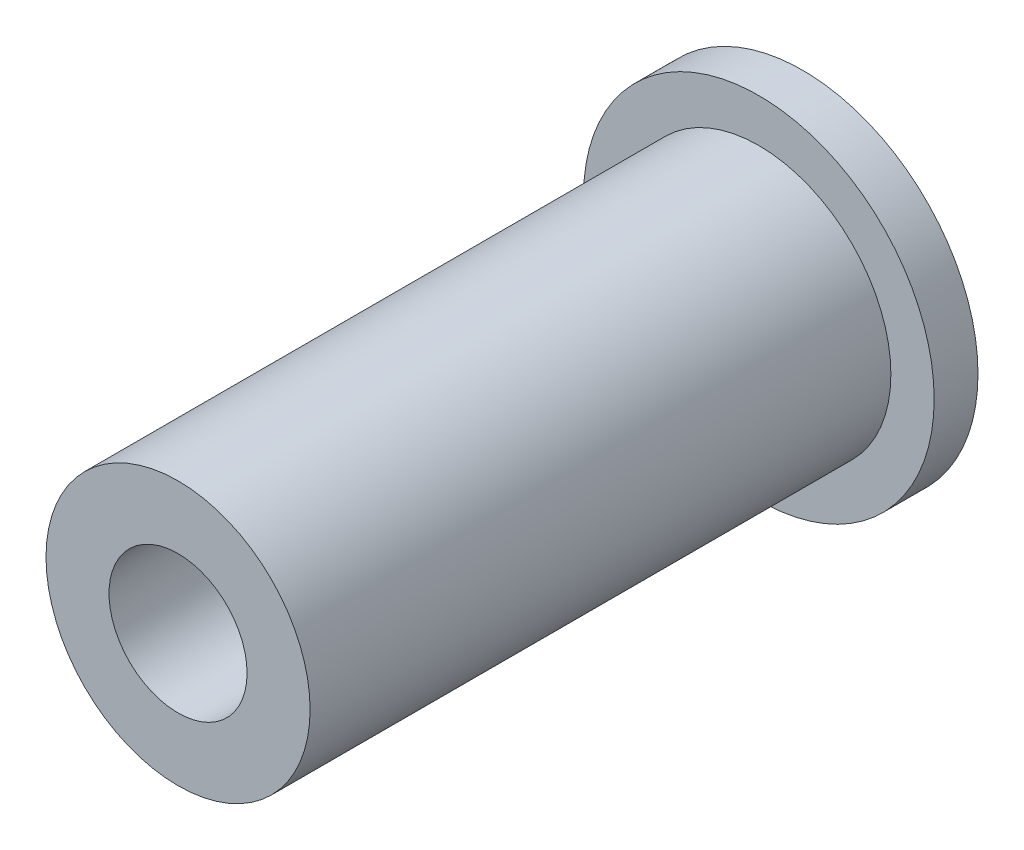
SolidWorks part; units mm, degrees
material "ABS"
ref_plane "Front Plane" through (0, 0, 0) normal (0, 0, 1) x (1, 0, 0)
ref_plane "Top Plane" through (0, 0, 0) normal (0, 1, 0) x (1, 0, 0)
ref_plane "Right Plane" through (0, 0, 0) normal (1, 0, 0) x (0, 0, -1)
sketch "Sketch1" plane through (0, 0, 0) normal (0, 0, 1) x (1, 0, 0)
  circle A0 centre (0, 0) radius 6.025
extrude "Boss-Extrude1" add sketch "Sketch1" along normal blind 10
sketch "Sketch2" plane through (0, 0, 10) normal (0, 0, 1) x (1, 0, 0)
  line L0 (0, -3.1496) -> (0, 3.1496) construction
  line L1 (2.7276, -1.5748) -> (-2.7276, 1.5748) construction
  line L2 (-2.7276, -1.5748) -> (2.7276, 1.5748) construction
  line L3 (0, 3.1496) -> (0.7493, 2.8395)
  line L4 (0.7493, 2.8395) -> (0.7846, 1.3589)
  line L5 (0.7846, 1.3589) -> (2.0845, 2.0687)
  line L6 (2.0845, 2.0687) -> (2.7276, 1.5748)
  line L7 (-1.9007, -3.2922) -> (2.1995, 3.8096) construction
  line L8 (2.7276, 1.5748) -> (2.8338, 0.7709)
  line L9 (2.8338, 0.7709) -> (1.5691, 0)
  line L10 (1.5691, 0) -> (2.8338, -0.7709)
  line L11 (2.8338, -0.7709) -> (2.7276, -1.5748)
  line L12 (2.7276, -1.5748) -> (2.0845, -2.0687)
  line L13 (2.0845, -2.0687) -> (0.7846, -1.3589)
  line L14 (0.7846, -1.3589) -> (0.7493, -2.8395)
  line L15 (0.7493, -2.8395) -> (0, -3.1496)
  line L16 (0, -3.1496) -> (-0.7493, -2.8395)
  line L17 (-0.7493, -2.8395) -> (-0.7846, -1.3589)
  line L18 (-0.7846, -1.3589) -> (-2.0845, -2.0687)
  line L19 (-2.0845, -2.0687) -> (-2.7276, -1.5748)
  line L20 (-2.7276, -1.5748) -> (-2.8338, -0.7709)
  line L21 (-2.8338, -0.7709) -> (-1.5691, 0)
  line L22 (-1.5691, 0) -> (-2.8338, 0.7709)
  line L23 (-2.8338, 0.7709) -> (-2.7276, 1.5748)
  line L24 (-2.7276, 1.5748) -> (-2.0845, 2.0687)
  line L25 (-2.0845, 2.0687) -> (-0.7846, 1.3589)
  line L26 (-0.7846, 1.3589) -> (-0.7493, 2.8395)
  line L27 (-0.7493, 2.8395) -> (0, 3.1496)
  circle A0 centre (0, 0) radius 3.1496
  point P7 (0, 0)
  point P9 (0, 0)
  point P12 (0, 0)
  point P16 (0, 0)
  point P18 (0, 0)
  point P45 (0, 0)
  dimension "D1" = 60
  dimension "D4" = 6.2992
  dimension "D2" = 60
  dimension "D3" = 1.7907
  dimension "D5" = 150
  dimension "D6" = 6
  dimension "D7" = 1.4986
extrude "Cut-Extrude1" cut sketch "Sketch2" against normal blind 10 contours L27 L26 L25 L24 L23 L22 L21 L20 L19 L18 L17 L16 L15 L14 L13 L12 L11 L10 L9 L8 L6 L5 L4 L3 region at (0, 0, 10)
sketch "Sketch3" plane through (0, 0, 10) normal (0, 0, 1) x (1, 0, 0)
  circle A0 centre (0, 0) radius 6.025
extrude "Boss-Extrude2" add sketch "Sketch3" along normal blind 16.5
sketch "Sketch4" plane through (0, 0, 26.5) normal (0, 0, 1) x (1, 0, 0)
  circle A0 centre (0, 0) radius 3.1496
extrude "Cut-Extrude2" cut sketch "Sketch4" against normal blind 16.5
sketch "Sketch5" plane through (0, 0, 0) normal (0, 0, -1) x (-1, 0, 0)
  circle A0 centre (0, 0) radius 8
extrude "Boss-Extrude3" add sketch "Sketch5" along normal blind 2
